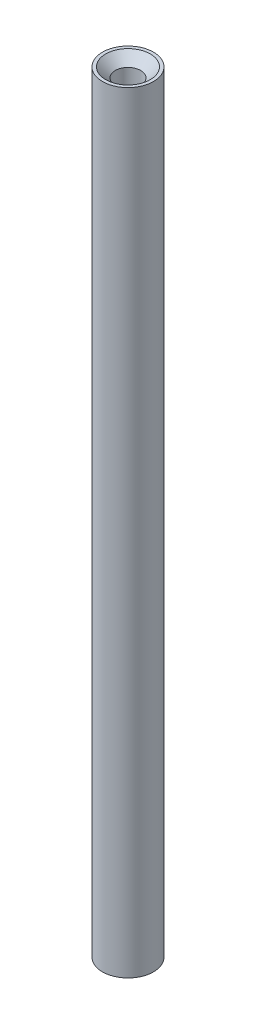
SolidWorks part; units mm, degrees
material "PTFE (general)"
ref_plane "Front" through (0, 0, 0) normal (0, 0, 1) x (1, 0, 0)
ref_plane "Top" through (0, 0, 0) normal (0, 1, 0) x (1, 0, 0)
ref_plane "Right" through (0, 0, 0) normal (1, 0, 0) x (0, 0, -1)
sketch "Sketch1" plane through (0, 0, 0) normal (0, 1, 0) x (1, 0, 0)
  circle A0 centre (0, 0) radius 2
  circle A1 centre (0, 0) radius 1
  dimension "D1" = 4
  dimension "D2" = 2
extrude "Boss-Extrude1" add sketch "Sketch1" along normal blind 60.5
chamfer "Chamfer1" distance 0.75 angle 45 1 edges at (0, 60.5, 1)
